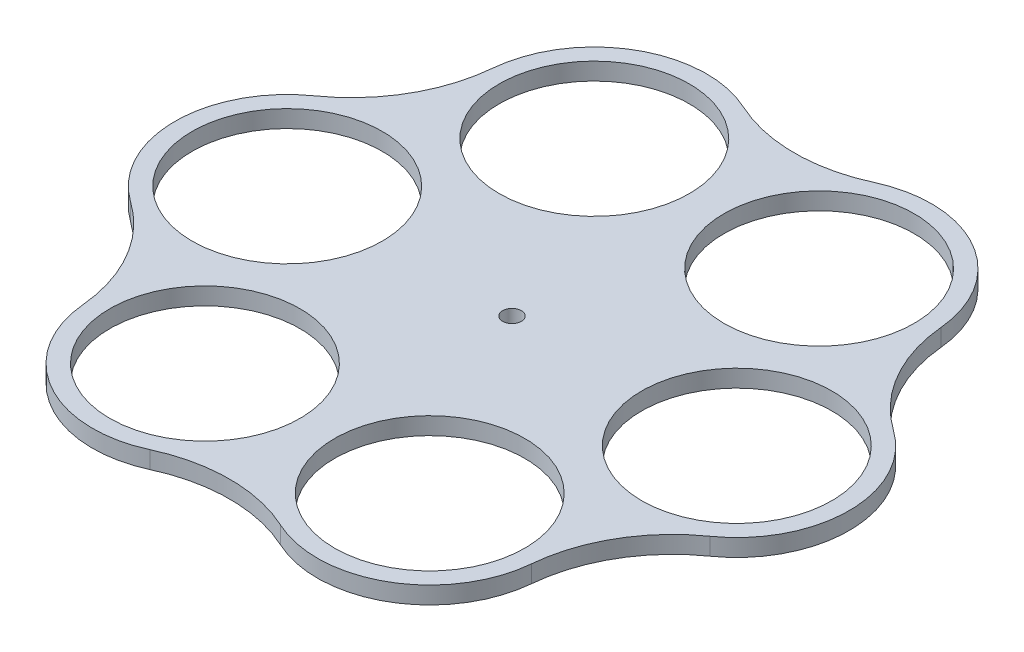
SolidWorks part; units mm, degrees
ref_plane "Front Plane" through (0, 0, 0) normal (0, 0, 1) x (1, 0, 0)
ref_plane "Top Plane" through (0, 0, 0) normal (0, 1, 0) x (1, 0, 0)
ref_plane "Right Plane" through (0, 0, 0) normal (1, 0, 0) x (0, 0, -1)
sketch "Sketch1" plane through (0, 0, 0) normal (0, 1, 0) x (1, 0, 0)
  circle A0 centre (-41.3791, 65.0217) radius 27.5
  circle A1 centre (-73.8791, 8.73) radius 27.5
  circle A2 centre (-41.3791, -47.5616) radius 27.5
  circle A3 centre (23.6209, -47.5616) radius 27.5
  circle A4 centre (56.1209, 8.73) radius 27.5
  circle A5 centre (23.6209, 65.0217) radius 27.5
  arc A6 (-73.7451, -50.5107) -> (-27.7501, -77.0659) centre (-41.3791, -47.5616) ccw
  arc A7 (-92.616, 35.2852) -> (-92.616, -17.8252) centre (-73.8791, 8.73) ccw
  arc A8 (-27.7501, 94.5259) -> (-73.7451, 67.9707) centre (-41.3791, 65.0217) ccw
  arc A9 (55.9868, 67.9707) -> (9.9918, 94.5259) centre (23.6209, 65.0217) ccw
  arc A10 (74.8578, -17.8252) -> (74.8578, 35.2852) centre (56.1209, 8.73) ccw
  arc A11 (9.9918, -77.0659) -> (55.9868, -50.5107) centre (23.6209, -47.5616) ccw
  arc A12 (-27.7501, 94.5259) -> (9.9918, 94.5259) centre (-8.8791, 135.3779) ccw
  arc A13 (55.9868, 67.9707) -> (74.8578, 35.2852) centre (100.8012, 72.054) ccw
  arc A14 (74.8578, -17.8252) -> (55.9868, -50.5107) centre (100.8012, -54.5939) ccw
  arc A15 (9.9918, -77.0659) -> (-27.7501, -77.0659) centre (-8.8791, -117.9179) ccw
  arc A16 (-73.7451, -50.5107) -> (-92.616, -17.8252) centre (-118.5594, -54.5939) ccw
  arc A17 (-92.616, 35.2852) -> (-73.7451, 67.9707) centre (-118.5594, 72.054) ccw
  circle A18 centre (-8.8791, 8.73) radius 2.7
extrude "Boss-Extrude1" add sketch "Sketch1" along normal blind 5
